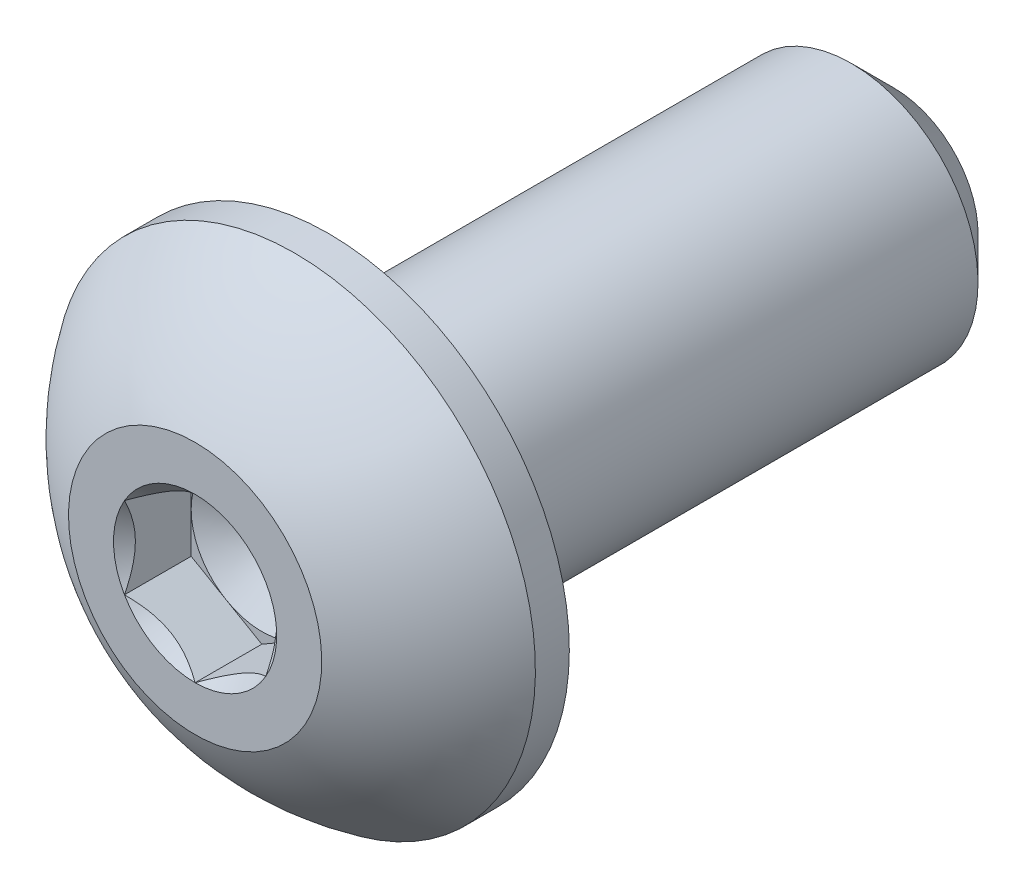
SolidWorks part; units mm, degrees
ref_plane "Front" through (0, 0, 0) normal (0, 0, 1) x (1, 0, 0)
ref_plane "Top" through (0, 0, 0) normal (0, 1, 0) x (1, 0, 0)
ref_plane "Right" through (0, 0, 0) normal (1, 0, 0) x (0, 0, -1)
sketch "Sketch1" plane through (0, 0, 0) normal (1, 0, 0) x (0, 0, -1)
  line L0 (0, 0) -> (-1.4986, 0) construction
  line L1 (0, 0) -> (6.35, 0)
  line L2 (0, 0) -> (0, 1.4224)
  line L3 (0, 1.4224) -> (6.35, 1.4224)
  line L4 (6.35, 0) -> (6.35, 1.4224)
  line L5 (0, -1.4224) -> (6.35, -1.4224) construction
  dimension "D1" = 6.35
  dimension "Thread Dia" = 2.8448
  dimension "Length" = 6.35
  dimension "Head Height" = 1.4986
revolve "Revolve1" add sketch "Sketch1" angle 360 about L0
ref_plane "Plane1" through (0, 0, 1.4986) normal (0, 0, 1) x (1, 0, 0)
chamfer "Chamfer1" distance 0.4763 angle 45 1 edges at (0, 1.4224, -6.35)
sketch "Sketch10" plane through (0, 0, 0) normal (1, 0, 0) x (0, 0, -1)
  line L0 (6.35, 1.4224) -> (6.9056, 1.4224)
  line L1 (6.9056, 1.4224) -> (6.6675, 1.01)
  line L2 (6.6675, 1.01) -> (6.5881, 1.01)
  line L3 (6.5881, 1.01) -> (6.35, 1.4224)
  line L4 (6.4691, 1.2162) -> (6.7866, 1.2162) construction
  dimension "D1" = 60
  dimension "D2" = 0.0794
  dimension "D3" = 0.3175
sketch "Sketch11" plane through (0, 0, -6.35) normal (0, 0, -1) x (-1, 0, 0)
  circle A1 centre (0, 0) radius 0.9461
  circle A2 centre (0, 0) radius 0.9461
  dimension "D1" = 0
curve "Helix/Spiral1" pitch 0.635 height 9.525 turns 15
sweep "Cut-Sweep1" [suppressed] cut profiles "Sketch10" path "Helix/Spiral1"
sketch "Sketch4" plane through (0, 0, 0) normal (0, 0, 1) x (1, 0, 0)
  circle A0 centre (0, 0) radius 2.7051
  dimension "Head Dia" = 5.4102
extrude "Extrude1" add sketch "Sketch4" along normal up to surface (1.4986 mm away) up to plane "Plane1"
sketch "Sketch9" plane through (0, 0, 0) normal (1, 0, 0) x (0, 0, -1)
  line L0 (0, 2.7051) -> (-0.381, 2.7051)
  line L1 (0, 2.7051) -> (0, 3.0861)
  line L2 (0, 3.0861) -> (-1.8796, 3.0861)
  line L3 (0, 0) -> (-1.4986, 0) construction
  line L4 (-1.8796, 3.0861) -> (-1.8796, 1.4224)
  line L5 (-1.8796, 1.4224) -> (-1.4986, 1.4224)
  line L6 (0, 0) -> (0, 1.4224) construction
  line L10 (0, 2.7051) -> (-1.4986, 2.7051) construction
  line L11 (0, 1.4224) -> (6.35, 1.4224) construction
  line L12 (-1.4986, 2.7051) -> (-1.4986, -2.7051) construction
  arc A0 (-1.4986, 1.4224) -> (-0.381, 2.7051) centre (1.4288, 0) cw
  dimension "Side Head Height" = 0.381
revolve "Cut-Revolve3" cut sketch "Sketch9" angle 360 about L3
sketch "Sketch6" plane through (0, 0, 1.4986) normal (0, 0, 1) x (1, 0, 0)
  line L1 (0, -0.9165) -> (0.7937, -0.4583)
  line L2 (0.7937, -0.4583) -> (0.7937, 0.4583)
  line L3 (0.7937, 0.4583) -> (0, 0.9165)
  line L4 (0, 0.9165) -> (-0.7938, 0.4583)
  line L5 (-0.7938, 0.4583) -> (-0.7938, -0.4583)
  line L6 (-0.7938, -0.4583) -> (0, -0.9165)
  circle A0 centre (0, 0) radius 0.7938 construction
  dimension "Hex" = 1.5875
extrude "Cut-Extrude1" cut sketch "Sketch6" against normal blind 0.7493
sketch "Sketch7" plane through (0, 0, 1.4986) normal (0, 0, 1) x (1, 0, 0)
  circle A0 centre (0, 0) radius 0.9165
extrude "Cut-Extrude4" cut sketch "Sketch7" against normal blind 0.7493 draft 45
sketch "Sketch8" plane through (0, 0, 0.7493) normal (0, 0, 1) x (1, 0, 0)
  circle A0 centre (0, 0) radius 0.7938 construction
  circle A1 centre (0, 0) radius 0.7938
extrude "Cut-Extrude5" cut sketch "Sketch8" against normal blind 0.2498 draft 60
sketch "Sketch12" [suppressed] plane through (0, 0, 0) normal (1, 0, 0) x (0, 0, -1)
  line L1 (0, -1.4224) -> (6.35, -1.4224) construction
  spline S0 degree 2 poles (5.8737, 0.013) (5.8319, 0.5945) (5.7944, 1.0058) (5.7415, 1.5865) (5.6885, 1.3739) (5.6356, 1.1614) (5.5827, 0.3681) (5.5298, -0.4251) (5.4769, -1.0058) (5.424, -1.5865) (5.371, -1.3739) (5.3181, -1.1614) (5.2652, -0.3681) (5.2123, 0.4251) (5.1594, 1.0058) (5.1065, 1.5865) (5.0535, 1.3739) (5.0006, 1.1614) (4.9477, 0.3681) (4.8948, -0.4251) (4.8419, -1.0058) (4.789, -1.5865) (4.736, -1.3739) (4.6831, -1.1614) (4.6302, -0.3681) (4.5773, 0.4251) (4.5244, 1.0058) (4.4715, 1.5865) (4.4185, 1.3739) (4.3656, 1.1614) (4.3127, 0.3681) (4.2598, -0.4251) (4.2069, -1.0058) (4.154, -1.5865) (4.101, -1.3739) (4.0481, -1.1614) (3.9952, -0.3681) (3.9423, 0.4251) (3.8894, 1.0058) (3.8365, 1.5865) (3.7835, 1.3739) (3.7306, 1.1614) (3.6777, 0.3681) (3.6248, -0.4251) (3.5719, -1.0058) (3.519, -1.5865) (3.466, -1.3739) (3.4131, -1.1614) (3.3602, -0.3681) (3.3073, 0.4251) (3.2544, 1.0058) (3.2015, 1.5865) (3.1485, 1.3739) (3.0956, 1.1614) (3.0427, 0.3681) (2.9898, -0.4251) (2.9369, -1.0058) (2.884, -1.5865) (2.831, -1.3739) (2.7781, -1.1614) (2.7252, -0.3681) (2.6723, 0.4251) (2.6194, 1.0058) (2.5665, 1.5865) (2.5135, 1.3739) (2.4606, 1.1614) (2.4077, 0.3681) (2.3548, -0.4251) (2.3019, -1.0058) (2.249, -1.5865) (2.196, -1.3739) (2.1431, -1.1614) (2.0902, -0.3681) (2.0373, 0.4251) (1.9844, 1.0058) (1.9315, 1.5865) (1.8785, 1.3739) (1.8256, 1.1614) (1.7727, 0.3681) (1.7198, -0.4251) (1.6669, -1.0058) (1.614, -1.5865) (1.561, -1.3739) (1.5081, -1.1614) (1.4552, -0.3681) (1.4023, 0.4251) (1.3494, 1.0058) (1.2965, 1.5865) (1.2435, 1.3739) (1.1906, 1.1614) (1.1377, 0.3681) (1.0848, -0.4251) (1.0319, -1.0058) (0.979, -1.5865) (0.926, -1.3739) (0.8731, -1.1614) (0.8202, -0.3681) (0.7673, 0.4251) (0.7144, 1.0058) (0.6615, 1.5865) (0.6085, 1.3739) (0.5556, 1.1614) (0.5027, 0.3681) (0.4498, -0.4251) (0.3969, -1.0058) (0.344, -1.5865) (0.291, -1.3739) (0.2381, -1.1614) (0.1852, -0.3681) (0.1323, 0.4251) (0.0794, 1.0058) (0.0419, 1.417) (0, 1.4223) knots 0.058478 0.058478 0.058478 0.066667 0.066667 0.077778 0.077778 0.088889 0.088889 0.1 0.1 0.111111 0.111111 0.122222 0.122222 0.133333 0.133333 0.144444 0.144444 0.155556 0.155556 0.166667 0.166667 0.177778 0.177778 0.188889 0.188889 0.2 0.2 0.211111 0.211111 0.222222 0.222222 0.233333 0.233333 0.244444 0.244444 0.255556 0.255556 0.266667 0.266667 0.277778 0.277778 0.288889 0.288889 0.3 0.3 0.311111 0.311111 0.322222 0.322222 0.333333 0.333333 0.344444 0.344444 0.355556 0.355556 0.366667 0.366667 0.377778 0.377778 0.388889 0.388889 0.4 0.4 0.411111 0.411111 0.422222 0.422222 0.433333 0.433333 0.444444 0.444444 0.455556 0.455556 0.466667 0.466667 0.477778 0.477778 0.488889 0.488889 0.5 0.5 0.511111 0.511111 0.522222 0.522222 0.533333 0.533333 0.544444 0.544444 0.555556 0.555556 0.566667 0.566667 0.577778 0.577778 0.588889 0.588889 0.6 0.6 0.611111 0.611111 0.622222 0.622222 0.633333 0.633333 0.644444 0.644444 0.655556 0.655556 0.666667 0.666667 0.674856 0.674856 0.674856 weights 0.948065 0.901259 1 0.866025 1 0.866025 1 0.866025 1 0.866025 1 0.866025 1 0.866025 1 0.866025 1 0.866025 1 0.866025 1 0.866025 1 0.866025 1 0.866025 1 0.866025 1 0.866025 1 0.866025 1 0.866025 1 0.866025 1 0.866025 1 0.866025 1 0.866025 1 0.866025 1 0.866025 1 0.866025 1 0.866025 1 0.866025 1 0.866025 1 0.866025 1 0.866025 1 0.866025 1 0.866025 1 0.866025 1 0.866025 1 0.866025 1 0.866025 1 0.866025 1 0.866025 1 0.866025 1 0.866025 1 0.866025 1 0.866025 1 0.866025 1 0.866025 1 0.866025 1 0.866025 1 0.866025 1 0.866025 1 0.866025 1 0.866025 1 0.866025 1 0.866025 1 0.866025 1 0.866025 1 0.866025 1 0.866025 1 0.901259 0.948065 construction
  point P0 (5.3966, -1.4224)
equation "\"D1@Cut-Extrude1\"=\"Head Height@Sketch1\"/2"
equation "\"D1@Cut-Extrude4\"=\"D1@Cut-Extrude1\""
equation "\"D1@Cut-Extrude5\"=\"D1@Cut-Extrude1\"/3"
equation "\"D3@Helix/Spiral1\" = \"Length@Sketch1\" + .125"
equation "\"D1@Chamfer1\" = \"D4@Helix/Spiral1\" * .75"
equation "\"D2@Sketch10\" = \"D4@Helix/Spiral1\" * .125"
equation "\"D3@Sketch10\" = \"D4@Helix/Spiral1\" * .5"
